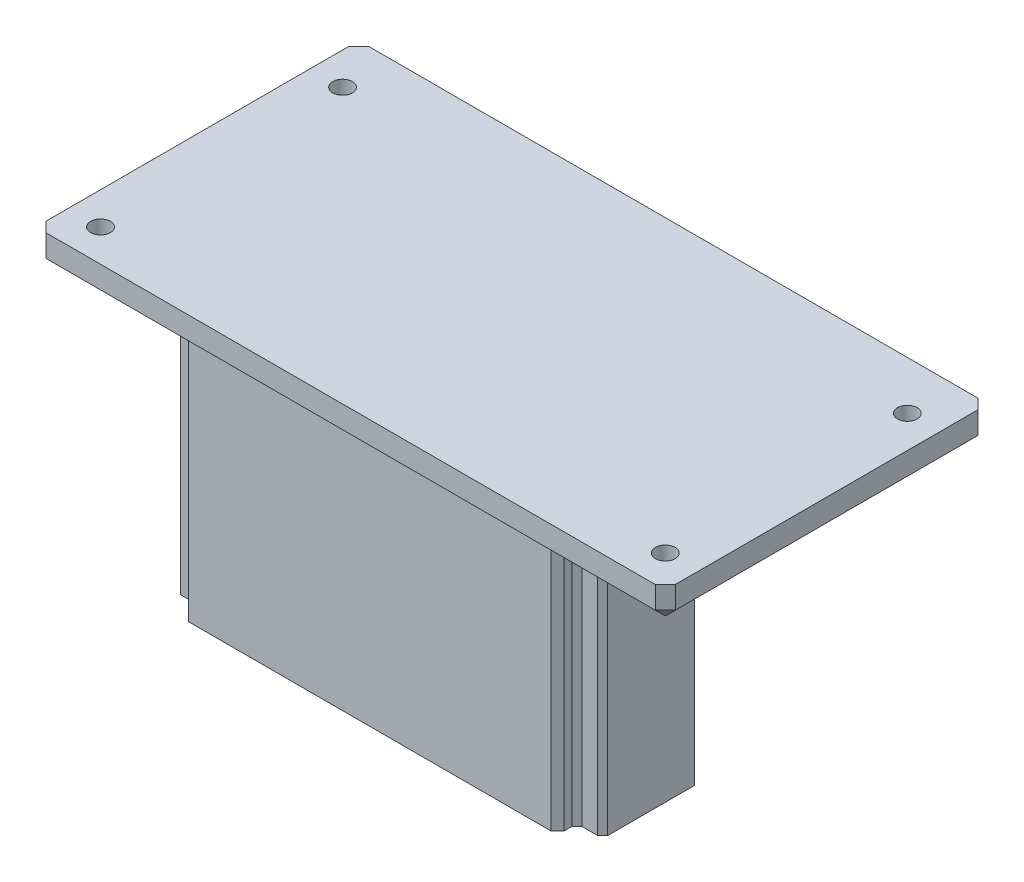
SolidWorks part; units mm, degrees
ref_plane "Front Plane" through (0, 0, 0) normal (0, 0, 1) x (1, 0, 0)
ref_plane "Top Plane" through (0, 0, 0) normal (0, 1, 0) x (1, 0, 0)
ref_plane "Right Plane" through (0, 0, 0) normal (1, 0, 0) x (0, 0, -1)
sketch "Sketch1" plane through (0, 0, 0) normal (0, 1, 0) x (1, 0, 0)
  line L0 (0, 47.5) -> (195, 47.5) construction
  line L1 (0, 0) -> (195, 0)
  line L2 (0, 0) -> (0, 95)
  line L3 (0, 95) -> (195, 95) construction
  line L4 (195, 0) -> (195, 95)
  line L5 (97.5, 95) -> (97.5, 0) construction
  line L7 (10, 85) -> (185, 85) construction
  line L8 (10, 85) -> (10, 10) construction
  line L9 (10, 10) -> (185, 10) construction
  line L10 (185, 85) -> (185, 10) construction
  line L11 (0, 95) -> (195, 95) construction
  line L12 (0, 95) -> (0, 100.5)
  line L13 (0, 100.5) -> (195, 100.5)
  line L14 (195, 95) -> (195, 100.5)
  circle A0 centre (10, 85) radius 3.05
  circle A1 centre (185, 85) radius 3.05
  circle A2 centre (185, 10) radius 3.05
  circle A3 centre (10, 10) radius 3.05
  dimension "D5" = 6.1
  dimension "D1" = 195
  dimension "D2" = 95
  dimension "D3" = 75
  dimension "D4" = 175
  dimension "D6" = 5.5
extrude "Boss-Extrude1" add sketch "Sketch1" along normal blind 10
sketch "Sketch2" plane through (0, 10, 0) normal (0, 1, 0) x (1, 0, 0)
  line L0 (43.7, 59) -> (91.1, 59)
  line L1 (41.7, 59) -> (41.7, 3.6) construction
  line L2 (41.7, 3.6) -> (158, 3.6)
  line L3 (158, 3.6) -> (158, 45.6) construction
  line L4 (91.1, 59) -> (91.1, 45.6)
  line L5 (91.1, 45.6) -> (158, 45.6)
  line L6 (158, 24.6) -> (41.7, 24.6) construction
  line L7 (158, 39.6) -> (166, 39.6)
  line L8 (158, 39.6) -> (158, 9.6) construction
  line L9 (158, 9.6) -> (166, 9.6)
  line L10 (166, 39.6) -> (166, 9.6)
  line L11 (99.85, 3.6) -> (99.85, 45.6) construction
  line L12 (41.7, 9.6) -> (33.7, 9.6)
  line L13 (33.7, 39.6) -> (33.7, 9.6)
  line L14 (41.7, 39.6) -> (33.7, 39.6)
  line L15 (41.7, 39.6) -> (41.7, 9.6) construction
  line L16 (41.7, 57) -> (41.7, 39.6)
  line L17 (41.7, 9.6) -> (41.7, 3.6)
  line L18 (158, 9.6) -> (158, 3.6)
  line L19 (158, 45.6) -> (158, 39.6)
  line L20 (81.7, 3.6) -> (81.7, 59) construction
  line L22 (61.7, 3.6) -> (61.7, 59) construction
  line L24 (195, 100.5) -> (0, 100.5) construction
  arc A0 (43.7, 59) -> (41.7, 57) centre (43.7, 57) ccw
  circle A1 centre (10, 85) radius 3.05 construction
  dimension "D6" = 2
  dimension "D11" = 42
  dimension "D1" = 116.3
  dimension "D2" = 8
  dimension "D3" = 49.4
  dimension "D4" = 13.4
  dimension "D5" = 30
  dimension "D7" = 40
  dimension "D8" = 20
  dimension "D9" = 51.7
  dimension "D10" = 41.5
extrude "Boss-Extrude2" add sketch "Sketch2" along normal blind 75.9 contours L16 L14 L13 L12 L17 L2 L18 L9 L10 L7 L19 L5 L4 L0 A0
sketch "Sketch3" plane through (0, 85.9, 0) normal (0, 1, 0) x (1, 0, 0)
  line L0 (99.85, 3.6) -> (99.85, 45.6) construction
  line L1 (33.7, 39.6) -> (41.7, 39.6) construction
  line L2 (33.7, 39.6) -> (33.7, 9.6) construction
  line L3 (33.7, 9.6) -> (41.7, 9.6) construction
  line L4 (41.7, 39.6) -> (41.7, 9.6) construction
  line L5 (41.7, 3.6) -> (158, 3.6) construction
  line L6 (91.1, 45.6) -> (158, 45.6) construction
  line L7 (37.7, 39.6) -> (37.7, 9.6) construction
  line L8 (33.7, 24.6) -> (41.7, 24.6) construction
  circle A0 centre (37.7, 32.1) radius 1.4
  circle A1 centre (37.7, 17.1) radius 1.4
  circle A2 centre (162, 17.1) radius 1.4
  circle A3 centre (162, 32.1) radius 1.4
  dimension "D1" = 2.8
  dimension "D2" = 7.5
extrude "Cut-Extrude1" cut sketch "Sketch3" against normal blind 6
chamfer "Chamfer1" distance 1.55 angle 45 8 edges at (41.7, 47.95, -9.6) (33.7, 47.95, -9.6) (33.7, 47.95, -39.6) (41.7, 47.95, -39.6) (166, 47.95, -9.6) (158, 47.95, -9.6) (158, 47.95, -39.6) (166, 47.95, -39.6)
chamfer "Chamfer2" distance 2 angle 45 3 edges at (41.7, 47.95, -3.6) (158, 47.95, -45.6) (158, 47.95, -3.6)
mirror "Mirror1" about plane through (0, 0, 0) normal (0, -1, 0) of "Chamfer2", "Chamfer1", "Cut-Extrude1", "Boss-Extrude2", "Boss-Extrude1"
sketch "Sketch4" plane through (0, 0, 0) normal (-1, 0, 0) x (0, 0, 1)
  line L1 (-125.9428, 106.1745) -> (9.0768, 106.1745)
  line L2 (-125.9428, 106.1745) -> (-125.9428, 0)
  line L3 (-125.9428, 0) -> (9.0768, 0)
  line L4 (9.0768, 106.1745) -> (9.0768, 0)
extrude "Cut-Extrude2" cut sketch "Sketch4" against normal through all
sketch "Sketch5" plane through (0, -10, 0) normal (0, -1, 0) x (1, 0, 0)
  line L0 (195, 0) -> (195, -100.5) construction
  line L1 (0, -100.5) -> (195, -100.5)
  line L2 (0, -100.5) -> (0, -100)
  line L3 (0, -100) -> (195, -100)
  line L4 (195, -100.5) -> (195, -100)
  dimension "D1" = 0.5
extrude "Cut-Extrude3" cut sketch "Sketch5" against normal through all
chamfer "Chamfer3" distance 3.1 angle 45 4 edges at (185, -10, -6.95) (185, -10, -88.05) (10, -10, -81.95) (10, -10, -13.05)
chamfer "Chamfer4" distance 3.1 angle 45 8 edges at (0, -5, 0) (0, -5, -100) (195, -5, 0) (195, -5, -100) (195, -10, -50) (97.5, -10, 0) (97.5, -10, -100) (0, -10, -50)
